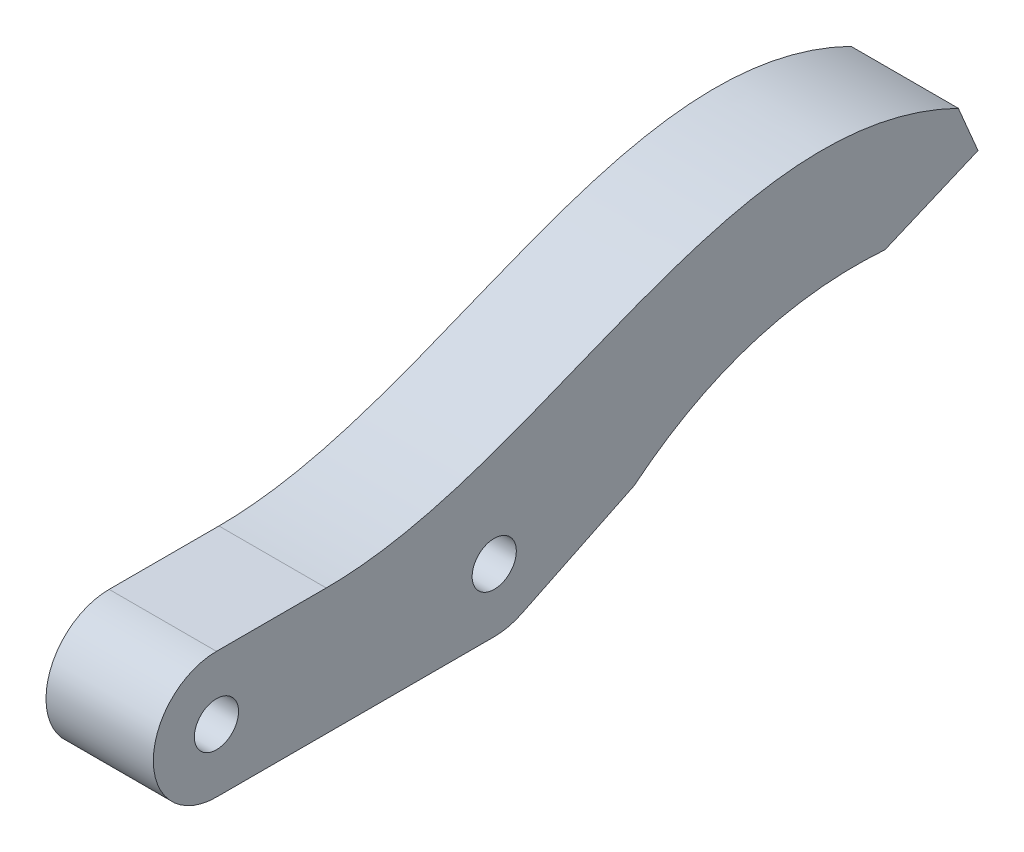
SolidWorks part; units mm, degrees
ref_plane "Front Plane" through (0, 0, 0) normal (0, 0, 1) x (1, 0, 0)
ref_plane "Top Plane" through (0, 0, 0) normal (0, 1, 0) x (1, 0, 0)
ref_plane "Right Plane" through (0, 0, 0) normal (1, 0, 0) x (0, 0, -1)
sketch "Sketch1" plane through (0, 0, 0) normal (1, 0, 0) x (0, 0, -1)
  line L1 (0, 0) -> (27, 0)
  line L2 (0, 0) -> (0, 10)
  line L3 (0, 10) -> (27, 10)
  circle A0 centre (5, 5) radius 1.75
  circle A1 centre (5, 5) radius 5
  circle A2 centre (27, 5) radius 5
  circle A3 centre (27, 5) radius 1.75
  dimension "D7" = 3.5
  dimension "D11" = 10
  dimension "D2" = 3.5
  dimension "D1" = 10
  dimension "D8" = 5
  dimension "D9" = 5
  dimension "D10" = 22
extrude "Boss-Extrude1" add sketch "Sketch1" along normal blind 8.5 contours A1 A0 | A2 L3 A1 L1 | A2 A3 | L2 A1 | L1 A1 region at (0, 5, -16) region at (0, 1.5645, -1.5645) region at (0, 5, -22.1414)
sketch "Sketch2" plane through (8.5, 0, 0) normal (1, 0, 0) x (0, 0, -1)
  line L6 (5, 10) -> (27, 10) construction
  line L14 (5, 10) -> (27, 10)
  line L20 (29.1838, 0.5021) -> (38.0854, 4.8241)
  line L21 (57.948, 11.0678) -> (65.3138, 14.1895)
  line L22 (65.3138, 14.1895) -> (63.753, 17.8724)
  arc A3 (27, 0) -> (27, 10) centre (27, 5) ccw construction
  arc A4 (27, 0) -> (27, 10) centre (27, 5) ccw
  spline S0 degree 2 poles (38.0854, 4.8241) (46.7975, 11.8952) (57.948, 11.0678) knots 0 0 0 1 1 1
  spline S1 degree 3 poles (63.753, 17.8724) (45.9289, 26.5638) (31.0593, 10) (13.695, 10) knots 0 0 0 0 1 1 1 1
  point P2 (27, 5)
  line M1 (27, 10) -> (5, 10)
  arc M4 (27, 0) -> (27, 10) centre (27, 5) ccw
  dimension "D3" = 4
  dimension "D4" = 8
extrude "Boss-Extrude2" add sketch "Sketch2" against normal blind 8.5 contours M1 M4 region at (8.5, 13.059, -44.3665)
